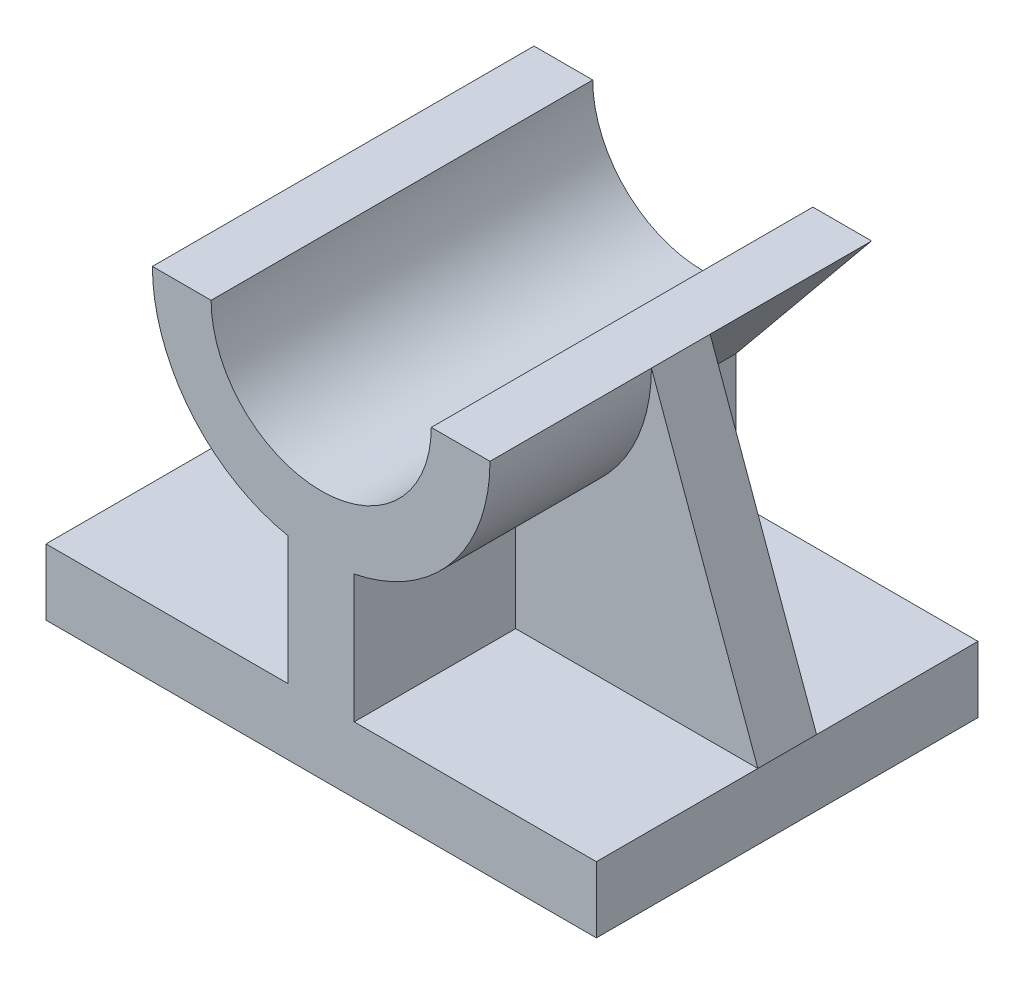
SolidWorks part; units mm, degrees
ref_plane "Front Plane" through (0, 0, 0) normal (0, 0, 1) x (1, 0, 0)
ref_plane "Top Plane" through (0, 0, 0) normal (0, 1, 0) x (1, 0, 0)
ref_plane "Right Plane" through (0, 0, 0) normal (1, 0, 0) x (0, 0, -1)
sketch "Sketch4" plane through (0, 0, 0) normal (0, 0, 1) x (1, 0, 0)
  line L0 (0, 0) -> (0, 44.5) construction
  line L1 (-37.5, 4.5) -> (-4.5, 4.5)
  line L2 (-37.5, 4.5) -> (-37.5, -4.5)
  line L3 (-37.5, -4.5) -> (37.5, -4.5)
  line L4 (37.5, 4.5) -> (37.5, -4.5)
  line L5 (-37.5, 4.5) -> (37.5, -4.5) construction
  line L6 (-37.5, -4.5) -> (37.5, 4.5) construction
  line L7 (-23, 44.5) -> (-15, 44.5)
  line L8 (15, 44.5) -> (23, 44.5)
  line L9 (-4.5, 4.5) -> (-4.5, 21.9445)
  line L10 (4.5, 4.5) -> (4.5, 21.9445)
  line L11 (-23, 44.5) -> (23, 44.5) construction
  line L12 (4.5, 4.5) -> (37.5, 4.5)
  arc A0 (-15, 44.5) -> (15, 44.5) centre (0, 44.5) ccw
  arc A1 (4.5, 21.9445) -> (23, 44.5) centre (0, 44.5) ccw
  arc A2 (-23, 44.5) -> (-4.5, 21.9445) centre (0, 44.5) ccw
  point P0 (0, 0)
  dimension "D4" = 30
  dimension "D5" = 46
  dimension "D1" = 9
  dimension "D2" = 75
  dimension "D3" = 44.5
  dimension "D6" = 9
  dimension "D7" = 4.5
extrude "Boss-Extrude3" add sketch "Sketch4" along normal blind 52
sketch "Sketch5" plane through (0, 0, 0) normal (0, 0, 1) x (1, 0, 0)
  line L0 (4.5, 4.5) -> (37.5, 4.5)
  line L1 (37.5, 4.5) -> (23, 44.5)
  line L2 (23, 44.5) -> (4.5, 21.9445)
  line L3 (4.5, 21.9445) -> (4.5, 4.5)
extrude "Boss-Extrude4" add sketch "Sketch5" along normal blind 30
extrude "Cut-Extrude1" cut sketch "Sketch5<2>" along normal blind 22
sketch "Sketch5<2>" plane through (0, 0, 0) normal (0, 0, 1) x (1, 0, 0) same geometry as "Sketch5"
